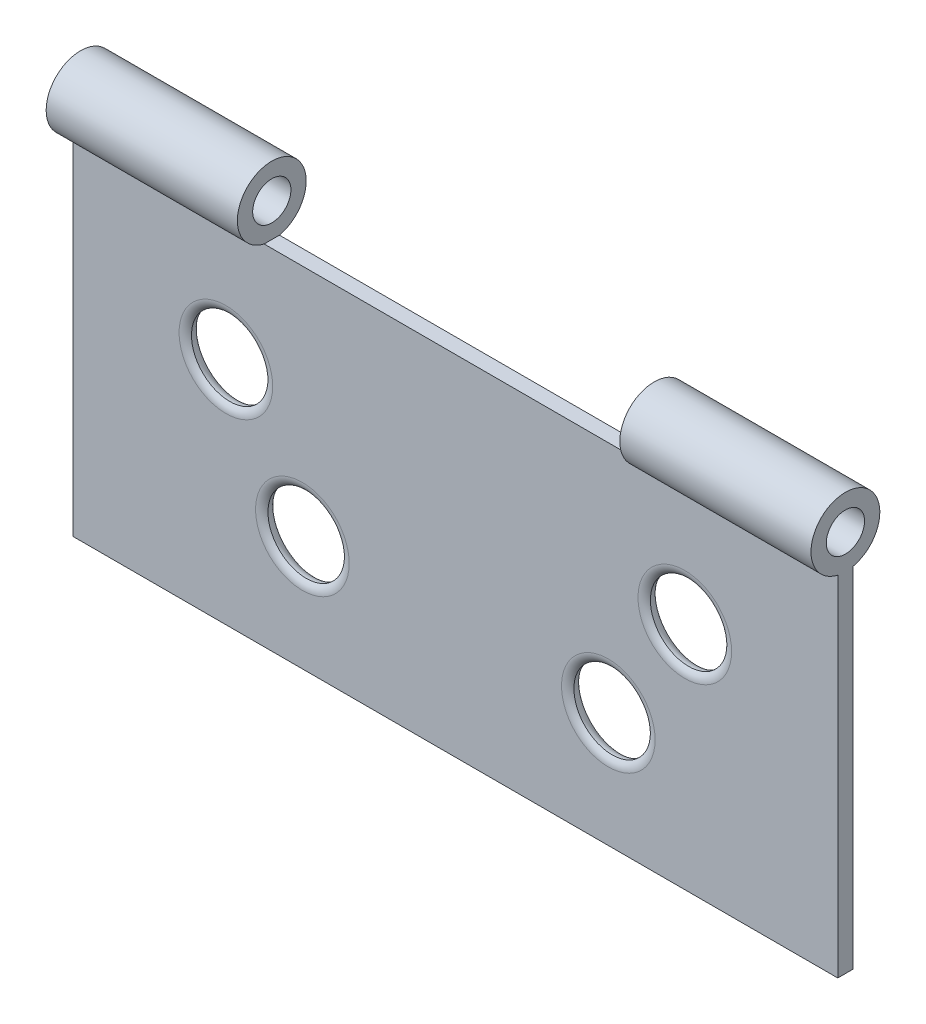
SolidWorks part; units mm, degrees
material "Liga de aço fundido"
ref_plane "Plano frontal" through (0, 0, 0) normal (0, 0, 1) x (1, 0, 0)
ref_plane "Plano superior" through (0, 0, 0) normal (0, 1, 0) x (1, 0, 0)
ref_plane "Plano direito" through (0, 0, 0) normal (1, 0, 0) x (0, 0, -1)
sketch "Esboço1" plane through (0, 0, 0) normal (0, 0, 1) x (1, 0, 0)
  line L0 (-6.1806, 8.1865) -> (-16.1806, 8.1865) construction
  line L2 (-9.6929, 8.1865) -> (-9.6929, 3.1865)
  line L3 (-9.6929, 3.1865) -> (-19.6929, 3.1865)
  line L4 (-19.6929, 8.1865) -> (-19.6929, 3.1865)
  line L5 (-19.6929, 8.1865) -> (-9.6929, 8.1865)
  circle A0 centre (-11.6929, 6.1896) radius 0.5
  circle A4 centre (-12.6929, 4.688) radius 0.5
  circle A5 centre (-17.6929, 6.1896) radius 0.5
  circle A6 centre (-16.6929, 4.6865) radius 0.5
  dimension "D3" = 1
  dimension "D8" = 1
  dimension "D9" = 1
  dimension "D10" = 1
  dimension "D11" = 1.5015
  dimension "D12" = 1.5
  dimension "D1" = 5
  dimension "D2" = 10
  dimension "D5" = 2
extrude "Ressalto-extrusão1" add sketch "Esboço1" along normal blind 0.2 contours L4 L3 L2 A0 region at (-14.6929, 5.7031, 0)
fillet "Filete1" radius 0.15 4 edges at (-16.1929, 4.6865, 0) (-17.1929, 6.1896, 0) (-12.1929, 4.688, 0) (-11.1929, 6.1896, 0)
fillet "Filete2" radius 0.15 4 edges at (-11.1929, 6.1896, 0.2) (-12.1929, 4.688, 0.2) (-17.1929, 6.1896, 0.2) (-16.1929, 4.6865, 0.2)
sketch "Esboço2" plane through (-9.6929, 0, 0) normal (1, 0, 0) x (0, 0, -1)
  line L0 (-0.2, 8.1865) -> (0, 8.1865) construction
  circle A0 centre (-0.1, 8.1865) radius 0.25
  circle A1 centre (-0.1, 8.1865) radius 0.45
  dimension "D1" = 0.2
extrude "Ressalto-extrusão2" add sketch "Esboço2" against normal blind 10
sketch "Esboço3" plane through (-9.6929, 0, 0) normal (1, 0, 0) x (0, 0, -1)
  arc A0 (0, 7.9574) -> (-0.2, 7.9574) centre (-0.1, 8.1865) ccw construction
  arc A1 (0, 7.9574) -> (-0.2, 7.9574) centre (-0.1, 8.1865) ccw
  circle A2 centre (-0.1, 8.1865) radius 0.25
  line M5 (-0.2, 8.1865) -> (-0.2, 7.9574)
  arc M6 (-0.2, 7.9574) -> (0, 7.9574) centre (-0.1, 8.1865) cw
  line M7 (0, 7.9574) -> (0, 8.1865)
  line M8 (0, 8.1865) -> (-0.2, 8.1865)
extrude "Corte-extrusão1" cut sketch "Esboço3" against normal blind 10 contours M5 M8 M7 M6 | A2 M5 M7 M8 region at (-9.6929, 8.2266, 0.1) region at (-9.6929, 8.0648, 0.1)
sketch "Esboço4" plane through (0, 0, 0) normal (0, 0, -1) x (-1, 0, 0)
  line L0 (12.1929, 7.7478) -> (9.6929, 7.7478)
  line L2 (12.1929, 7.7478) -> (12.1929, 9.2478)
  line L3 (12.1929, 9.2478) -> (17.1929, 9.2478)
  line L4 (19.6929, 3.1865) -> (19.6929, 7.7478)
  line L5 (19.6929, 7.7478) -> (9.6929, 7.7478)
  line L6 (9.6929, 7.7478) -> (9.6929, 3.1865)
  line L7 (9.6929, 3.1865) -> (19.6929, 3.1865)
  line L8 (19.6929, 3.1865) -> (19.6929, 7.7478)
  line L9 (19.6929, 7.7478) -> (17.1929, 7.7478)
  line L10 (9.6929, 7.7478) -> (9.6929, 3.1865)
  line L11 (9.6929, 3.1865) -> (19.6929, 3.1865)
  line L12 (17.1929, 7.7478) -> (17.1929, 9.2478)
  line M10 (19.6929, 7.7478) -> (9.6929, 7.7478)
  dimension "D2" = 2.5
  dimension "D3" = 2.5
  dimension "D1" = 0
extrude "Corte-extrusão2" cut sketch "Esboço4" against normal blind 10 and the other way blind 10 contours L12 L3 L2 M10 region at (-14.6929, 8.4978, 0)
